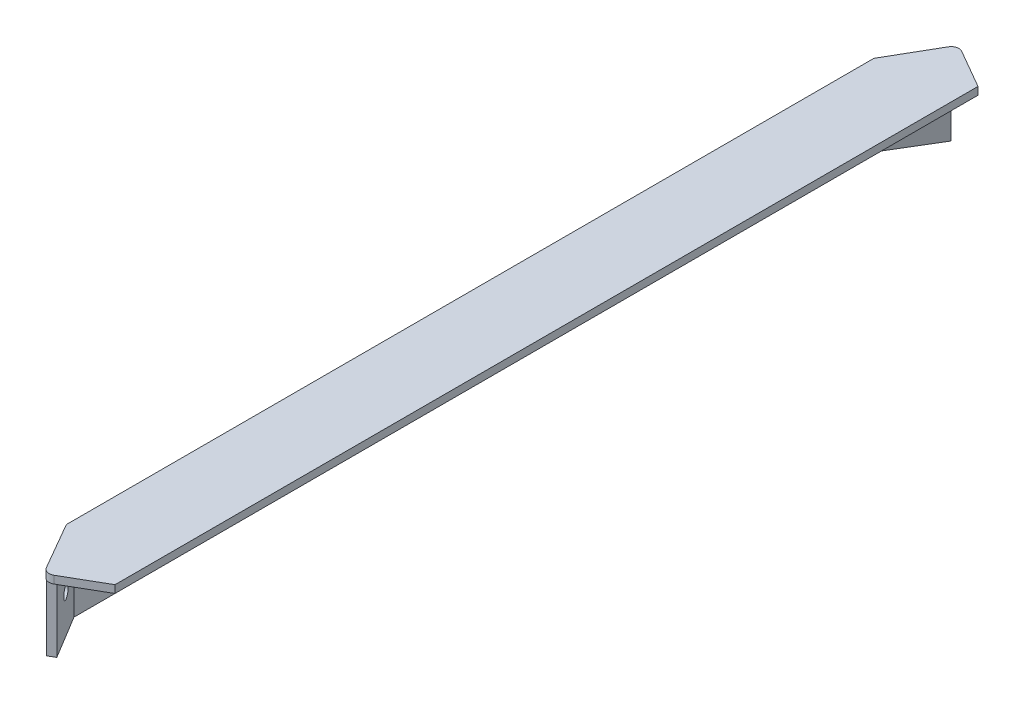
SolidWorks part; units mm, degrees
ref_plane "Front Plane" through (0, 0, 0) normal (0, 0, 1) x (1, 0, 0)
ref_plane "Top Plane" through (0, 0, 0) normal (0, 1, 0) x (1, 0, 0)
ref_plane "Right Plane" through (0, 0, 0) normal (1, 0, 0) x (0, 0, -1)
sketch "Sketch1" plane through (0, 0, 0) normal (0, 0, 1) x (1, 0, 0)
  line L6 (0, 0) -> (0, 70)
  line L7 (0, 70) -> (70, 70)
  line L8 (70, 70) -> (70, 63)
  line L9 (70, 63) -> (7, 63)
  line L10 (7, 63) -> (7, 0)
  line L11 (7, 0) -> (0, 0)
  dimension "D1" = 70
  dimension "D2" = 70
  dimension "D3" = 7
  dimension "D4" = 7
extrude "Boss-Extrude1" add sketch "Sketch1" along normal blind 370
sketch "Sketch2" plane through (0, 0, 0) normal (0, 1, 0) x (1, 0, 0)
  line L0 (0, -370) -> (25, -413.3013)
  line L1 (25, -413.3013) -> (31.0622, -409.8013)
  line L2 (31.0622, -409.8013) -> (7, -370)
  line L3 (0, -370) -> (7, -370) construction
  line L4 (7, -370) -> (0, -370)
  line L5 (0, -370) -> (0, 0) construction
  dimension "D1" = 46.5095
  dimension "D2" = 50
  dimension "D3" = 210
  dimension "D4" = 7
extrude "Boss-Extrude2" add sketch "Sketch2" along normal blind 63
sketch "Sketch9" plane through (0, 63, 0) normal (0, 1, 0) x (1, 0, 0)
  line L0 (0, -370) -> (25, -413.3013)
  line L1 (34.5622, -415.8634) -> (70, -395.4034)
  line L2 (70, -395.4034) -> (70, -370)
  line L3 (70, -370) -> (0, -370)
  arc A0 (25, -413.3013) -> (34.5622, -415.8634) centre (31.0622, -409.8013) ccw
  dimension "D5" = 14
  dimension "D2" = 40.9201
  dimension "D1" = 90
  dimension "D3" = 90
  dimension "D4" = 60
  dimension "D6" = 7
  dimension "D7" = 7
extrude "Boss-Extrude4" add sketch "Sketch9" along normal blind 7
sketch "Sketch10" plane through (-158.6877, 0, 95.9359) normal (0.8558, 0, -0.5174) x (-0.5174, 0, -0.8558)
  line L0 (-366.7649, 63) -> (-366.7649, 0) construction
  line L1 (-366.7649, 0) -> (-320.2554, 0) construction
  circle A0 centre (-341.7649, 35) radius 6
  dimension "D1" = 12
  dimension "D2" = 25
  dimension "D3" = 35
extrude "Cut-Extrude3" cut sketch "Sketch10" against normal blind 7
sketch "Sketch21" plane through (0, 0, 0) normal (0, 0, -1) x (-1, 0, 0)
  line L0 (0, 70) -> (-70, 70) construction
  line L1 (-70, 70) -> (-70, 0) construction
  line L2 (-70, 0) -> (0, 0) construction
  line L3 (0, 0) -> (0, 69.2595) construction
fillet "Fillet5" radius 5 2 edges at (19.0311, 63, 389.9006) (7, 63, 185)
mirror "Mirror6" about plane through (0, 0, 0) normal (0, 0, 1) of bodies 107 108
